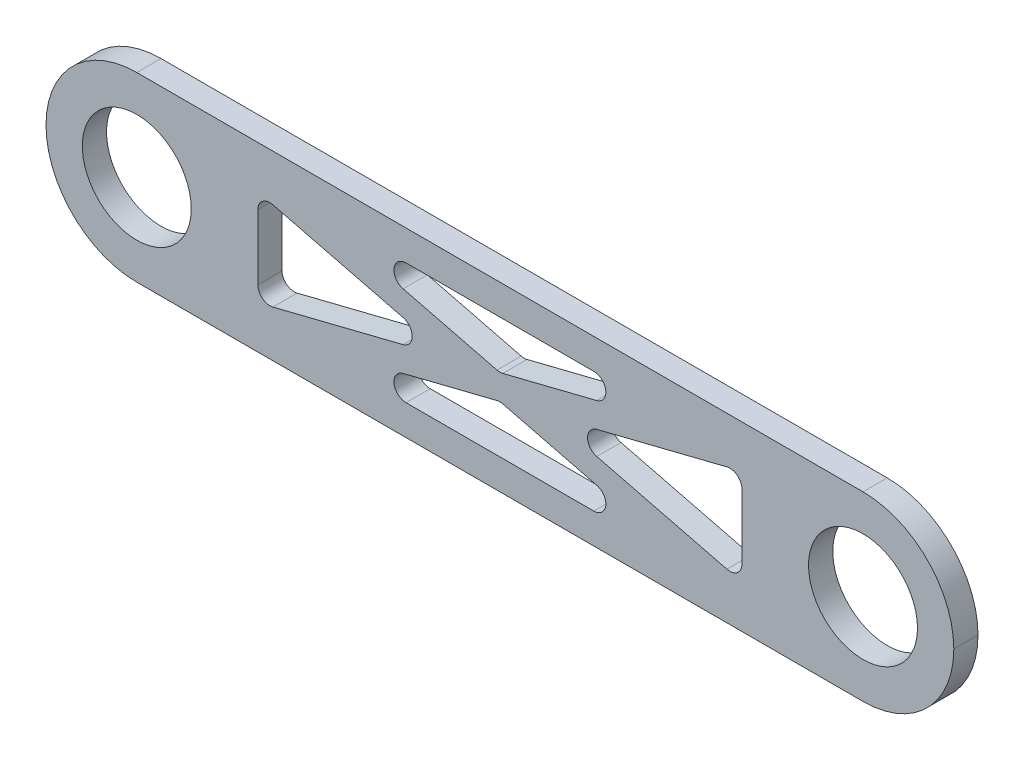
SolidWorks part; units mm, degrees
material "Thornel Mat VMA"
ref_plane "前视基准面" through (0, 0, 0) normal (0, 0, 1) x (1, 0, 0)
ref_plane "上视基准面" through (0, 0, 0) normal (0, 1, 0) x (1, 0, 0)
ref_plane "右视基准面" through (0, 0, 0) normal (1, 0, 0) x (0, 0, -1)
sketch "草图1" plane through (0, 0, 0) normal (0, 0, 1) x (1, 0, 0)
  line L1 (-37.5, -7.5) -> (37.5, -7.5)
  line L2 (-37.5, -7.5) -> (-37.5, 7.5)
  line L3 (-37.5, 7.5) -> (37.5, 7.5)
  line L4 (37.5, -7.5) -> (37.5, 7.5)
  line L5 (-37.5, -7.5) -> (37.5, 7.5) construction
  line L6 (-37.5, 7.5) -> (37.5, -7.5) construction
  point P0 (0, 0)
  dimension "D1" = 75
  dimension "D2" = 15
extrude "凸台-拉伸1" add sketch "草图1" along normal blind 2
fillet "圆角1" radius 7.5 4 edges at (37.5, -7.5, 1) (-37.5, -7.5, 1) (-37.5, 7.5, 1) (37.5, 7.5, 1)
sketch "草图2" plane through (0, 0, 2) normal (0, 0, 1) x (1, 0, 0)
  circle A0 centre (30, 0) radius 4.5
  circle A1 centre (-30, 0) radius 4.5
  dimension "D1" = 9
  dimension "D2" = 9
  dimension "D3" = 60
extrude "切除-拉伸1" cut sketch "草图2" against normal blind 2
sketch "草图3" plane through (0, 0, 2) normal (0, 0, 1) x (1, 0, 0)
  line L0 (-15.8769, -5) -> (0, -1.0308)
  line L1 (-15.8769, -5) -> (15.8769, -5)
  line L2 (-20, -3.9692) -> (-20, 3.9692)
  line L3 (-15.8769, 5) -> (15.8769, 5)
  line L4 (20, -3.9692) -> (20, 3.9692)
  line L5 (-20, -5) -> (20, 5) construction
  line L6 (-20, 5) -> (20, -5) construction
  line L7 (-20, 3.9692) -> (-4.1231, 0)
  line L8 (-20.2425, -4.0299) -> (-4.1231, 0)
  line L9 (-15.8769, 5) -> (0, 1.0308)
  line L10 (0, 1.0308) -> (15.8769, 5)
  line L11 (-19.7575, 5.9701) -> (20.2425, -4.0299) construction
  line L12 (-20.2425, 4.0299) -> (19.7575, -5.9701) construction
  line L13 (-19.7575, -5.9701) -> (20.2425, 4.0299) construction
  line L14 (-20.2425, -4.0299) -> (19.7575, 5.9701) construction
  line L15 (4.1231, 0) -> (20, -3.9692)
  line L16 (4.1231, 0) -> (20, 3.9692)
  line L17 (0, -1.0308) -> (15.8769, -5)
  point P0 (0, 0)
  dimension "D1" = 40
  dimension "D2" = 10
  dimension "D3" = 1
  dimension "D4" = 1
extrude "切除-拉伸2" cut sketch "草图3" against normal blind 10 contours L16 L15 L4 | L9 L10 L3 | L17 L0 L1 | L2 L8 L7 region at (0, -3.6769, 2) region at (-14.7077, 0, 2) region at (0, 3.6769, 2) region at (14.7077, 0, 2)
fillet "圆角2" radius 1 12 edges at (-15.8769, -5, 1) (0, -1.0308, 1) (15.8769, -5, 1) (-4.1231, 0, 1) (-20, -3.9692, 1) (-20, 3.9692, 1) (4.1231, 0, 1) (20, 3.9692, 1) (-15.8769, 5, 1) (15.8769, 5, 1) (0, 1.0308, 1) (20, -3.9692, 1)
